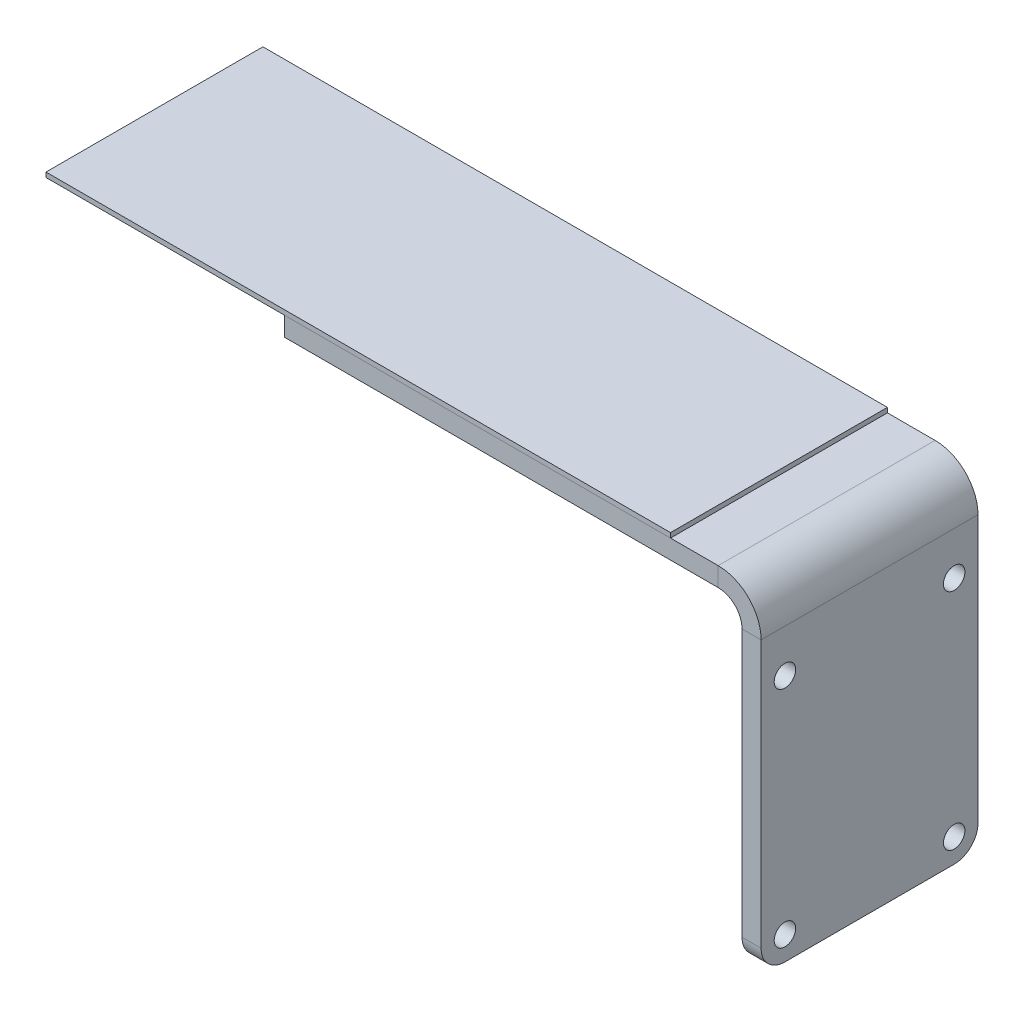
SolidWorks part; units mm, degrees
note: The reader was unsure of these and kept them because the rebuilt part matched: thickness of "Base-Flange1", "Edge-Flange1", "Sheet-Metal1", "Sheet-Metal2"; flange length of "Edge-Flange1".
ref_plane "Front Plane" through (0, 0, 0) normal (0, 0, 1) x (1, 0, 0)
ref_plane "Top Plane" through (0, 0, 0) normal (0, 1, 0) x (1, 0, 0)
ref_plane "Right Plane" through (0, 0, 0) normal (1, 0, 0) x (0, 0, -1)
sketch "Sketch1" plane through (0, 0, 0) normal (1, 0, 0) x (0, 0, -1)
  line L0 (-17.75, -30) -> (-22.75, -30) construction
  line L1 (-22.75, -35) -> (22.75, -35)
  line L2 (-22.75, -35) -> (-22.75, 35)
  line L3 (-22.75, 35) -> (22.75, 35)
  line L4 (22.75, -35) -> (22.75, 35)
  line L5 (-22.75, -35) -> (22.75, 35) construction
  line L6 (-22.75, 35) -> (22.75, -35) construction
  line L7 (17.75, 19.25) -> (17.75, -32.25) construction
  line L8 (-17.75, -35) -> (-17.75, -30) construction
  line L9 (-20, -30) -> (20, -30) construction
  circle A0 centre (-17.75, -30) radius 2.25
  circle A1 centre (17.75, -30) radius 2.25
  circle A2 centre (17.75, 17) radius 2.25
  circle A3 centre (-17.75, 17) radius 2.25
  point P0 (0, 0)
  point P19 (0, -30)
  dimension "D6" = 4.5
  dimension "D1" = 45.5
  dimension "D2" = 70
  dimension "D3" = 40
  dimension "D4" = 51.5
base flange "Base-Flange1" sketch "Sketch1" thickness 4 reverse thickness direction no parameters "D1"=5
edge flange "Edge-Flange1" sketch "Sketch8" flange angle 90 flange length 100 flange position material inside bend radius 5 thickness 4 relief rectangular parameters "D1"=0.7366, "D6"=10
sketch "Sketch8" plane through (-4, 35, 0) normal (0, -1, 0) x (0, 0, 1)
  line L2 (-22.75, 0) -> (-22.75, 96)
  line L3 (-22.75, 96) -> (22.75, 96)
  line L4 (22.75, 96) -> (22.75, 0)
  line L5 (22.75, 0) -> (-22.75, 0) construction
  line L6 (22.75, 0) -> (-22.75, 0)
bend "EdgeBend1" bend radius 5 bend angle 90 parameters "D5"=1
sketch "Sketch9" plane through (0, 35, 0) normal (0, 1, 0) x (1, 0, 0)
  line L0 (-4, 22.75) -> (-100, 22.75) construction
  line L1 (-19, 22.75) -> (-150, 22.75)
  line L2 (-19, 22.75) -> (-19, -22.75)
  line L3 (-19, -22.75) -> (-150, -22.75)
  line L4 (-150, 22.75) -> (-150, -22.75)
  line L5 (-9, -22.75) -> (-9, 22.75) construction
  line L6 (0, 22.75) -> (0, -22.75) construction
  line L7 (-9, -22.75) -> (-100, -22.75) construction
  dimension "D1" = 10
  dimension "D2" = 150
extrude "Boss-Extrude1" add sketch "Sketch9" along normal blind 1 separate body
fillet "Fillet1" radius 5 2 edges at (-2, -35, -22.75) (-2, -35, 22.75)
sketch "Bend-Lines1" [suppressed] plane through (0, 0, 0) normal (0, 1, 0) x (1, 0, 0)
sketch "Bounding-Box1" [suppressed] plane through (0, 0, 0) normal (0, 1, 0) x (1, 0, 0)
sheet metal parameters "Sheet-Metal1" thickness 4 parameters "D1"=0.7366, "D7"=2
flat pattern "Flat-Pattern1" [suppressed]
sketch "Bend-Lines2" plane through (0, 0, 0) normal (0, 1, 0) x (1, 0, 0)
sketch3d "Bounding-Box2" [suppressed]
  line L0 (-22.75, 35, 0) -> (-22.75, -35, 0) construction
  line L1 (22.75, 35, 0) -> (22.75, -35, 0) construction
  line L2 (-22.75, 35, 0) -> (22.75, 35, 0) construction
  line L3 (-22.75, -35, 0) -> (22.75, -35, 0) construction
sheet metal parameters "Sheet-Metal2" thickness 4 parameters "D1"=0.7366, "D7"=2
flat pattern "Flat-Pattern1"
sketch "Bend-Lines2" plane through (0, 0, 0) normal (1, 0, 0) x (0, 0, -1)
  line L0 (-22.75, 33.0686) -> (22.75, 33.0686) construction
  line L1 (-22.75, 33.0686) -> (22.75, 33.0686) construction
sketch3d "Bounding-Box2" [suppressed]
  line L0 (-22.7499, -35, 0) -> (-22.75, 131.1372, 0) construction
  line L1 (22.75, -35, 0) -> (22.7499, 131.1372, 0) construction
  line L2 (-22.7499, -35, 0) -> (22.75, -35, 0) construction
  line L3 (-22.75, 131.1372, 0) -> (22.7499, 131.1372, 0) construction
bend of the flat pattern "Flatten-<EdgeBend1>1"
